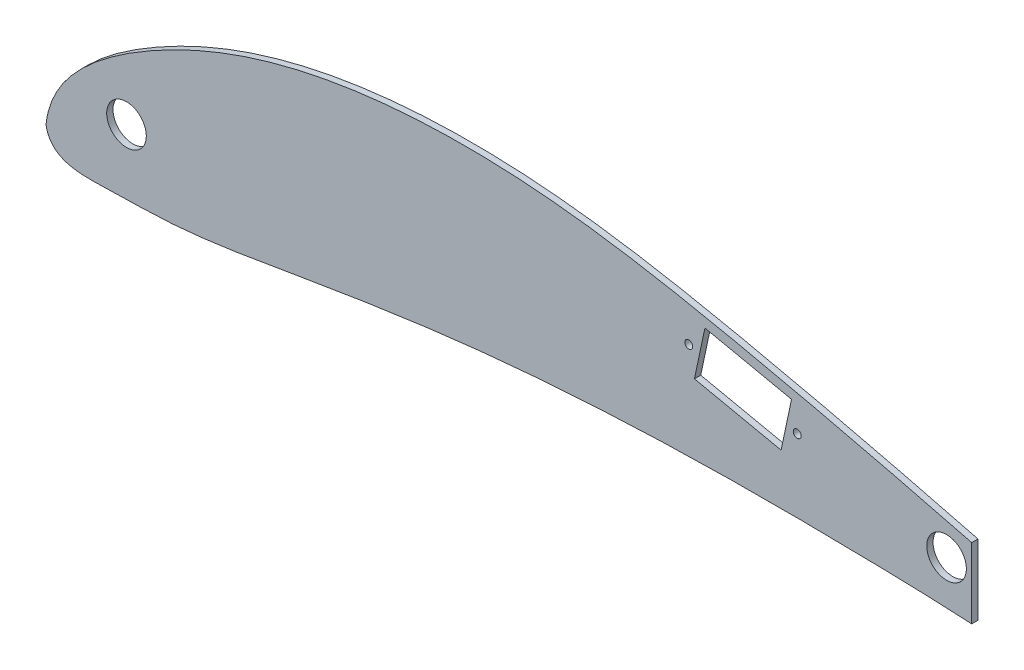
SolidWorks part; units mm, degrees
material "Balsa"
ref_plane "Front Plane" through (0, 0, 0) normal (0, 0, 1) x (1, 0, 0)
ref_plane "Top Plane" through (0, 0, 0) normal (0, 1, 0) x (1, 0, 0)
ref_plane "Right Plane" through (0, 0, 0) normal (1, 0, 0) x (0, 0, -1)
sketch "Sketch1" plane through (0, 0, 0) normal (0, 0, 1) x (1, 0, 0)
  spline S0 degree 3 poles (0.0006, 0.0001) (0.8106, 7.3592) (8.6491, 17.8566) (26.2867, 29.9752) (52.1111, 42.0692) (89.5976, 49.2908) (131.4008, 47.8848) (173.2567, 40.0411) (217.9611, 29.613) (256.9521, 19.5289) (290.3598, 8.711) (301.2732, 4.3828) (314.8169, -0.5162) (309.8463, 0.0001) knots 0 0 0 0 0.060864 0.113688 0.188609 0.312909 0.448482 0.557612 0.691544 0.852438 0.929756 0.976058 1 1 1 1
  spline S1 degree 3 poles (309.8463, 0.0001) (303.9568, 1.471) (293.9895, 2.094) (276.264, 4.5144) (260.8463, 5.4274) (235.8588, 7.8703) (205.1014, 8.8381) (157.7186, 9.0307) (110.4973, 6.1815) (66.5062, -0.5867) (36.4547, -6.0985) (15.3166, -6.1891) (1.2307, -6.9241) (0.0006, 0.0001) knots 0 0 0 0 0.057787 0.095275 0.171021 0.205339 0.335319 0.464904 0.658702 0.785512 0.893517 0.943092 1 1 1 1
extrude "Boss-Extrude1" add sketch "Sketch1" along normal blind 1.5875
sketch "Sketch2" plane through (0, 0, 1.5875) normal (0, 0, 1) x (1, 0, 0)
  circle A0 centre (20.32, 10.16) radius 5
  circle A1 centre (227.2963, 19.0501) radius 5
  dimension "D2" = 10
  dimension "D3" = 10
  dimension "D6" = 20.32
  dimension "D1" = 82.55
  dimension "D4" = 19.05
  dimension "D5" = 10.16
extrude "Cut-Extrude1" cut sketch "Sketch2" against normal through all
sketch "Sketch3" plane through (0, 0, 1.5875) normal (0, 0, 1) x (1, 0, 0)
  line L1 (350.4863, -6.3499) -> (233.6463, -6.3499)
  line L2 (350.4863, -6.3499) -> (350.4863, 44.4501)
  line L3 (350.4863, 44.4501) -> (233.6463, 44.4501)
  line L4 (233.6463, -6.3499) -> (233.6463, 44.4501)
  circle A0 centre (227.2963, 19.0501) radius 5 construction
  dimension "D1" = 6.35
  dimension "D2" = 116.84
  dimension "D3" = 50.8
  dimension "D4" = 44.45
extrude "Cut-Extrude2" cut sketch "Sketch3" against normal through all contours L3 L4 L1 L2
sketch "Sketch4" plane through (0, 0, 1.5875) normal (0, 0, 1) x (1, 0, 0)
  line L0 (164.9866, 32.4719) -> (162.2243, 33.059) construction
  line L1 (166.3069, 38.6831) -> (188.1704, 34.0358)
  line L2 (166.3069, 38.6831) -> (163.6664, 26.2606)
  line L3 (163.6664, 26.2606) -> (185.5299, 21.6134)
  line L4 (188.1704, 34.0358) -> (185.5299, 21.6134)
  line L5 (186.8502, 27.8246) -> (189.6125, 27.2375) construction
  circle A0 centre (189.6125, 27.2375) radius 1
  circle A1 centre (162.2243, 33.059) radius 1
  dimension "D4" = 2
  dimension "D1" = 28
  dimension "D2" = 22.352
  dimension "D3" = 12.7
extrude "Cut-Extrude3" cut sketch "Sketch4" against normal through all
